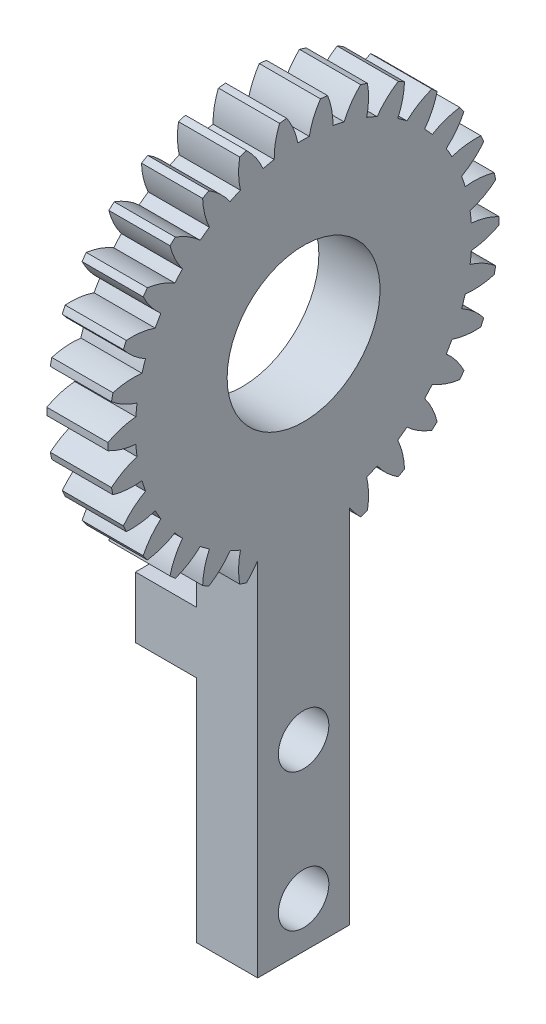
SolidWorks part; units mm, degrees
ref_plane "Plane1" through (0, 0, 0) normal (0, 0, 1) x (1, 0, 0)
ref_plane "Plane2" through (0, 0, 0) normal (0, 1, 0) x (1, 0, 0)
ref_plane "Plane3" through (0, 0, 0) normal (1, 0, 0) x (0, 0, -1)
other "Configuration Table"
sketch "HoldingSke" plane through (0, 0, 0) normal (0, 1, 0) x (1, 0, 0)
  line L0 (0, 0) -> (1.0825, -0.625)
  line L1 (-15, 0) -> (100, 0) construction
  line L2 (0, 0) -> (-2.1039, 2.3779)
  line L3 (0, 0) -> (-11.863, 4.5341)
  line L4 (0, 0) -> (7.479, 4.318)
  line L5 (0, 0) -> (-46.8476, -17.4728)
  line L6 (0, 0) -> (-3.3159, -2.2372)
  line L7 (-2.1039, 2.3779) -> (8.6586, 51.2059)
  line L8 (-76.2, 54.61) -> (-74.4, 54.61)
  line L9 (-71.009, 38.7566) -> (-53.1078, 45.2721)
  line L10 (-76.2, 71.12) -> (104.1128, 71.12)
  line L11 (0, 0) -> (-4, 0)
  line L12 (-76.2, 101.6) -> (-76.17, 101.6)
  line L13 (24.9733, 27.94) -> (52.9518, 28.4284)
  line L14 (24.9733, 27.94) -> (24.9743, 27.94)
  line L15 (24.9733, 27.94) -> (100.4006, 29.5858)
  line L16 (-63.627, -0.8) -> (-12.827, -0.8)
  circle A0 centre (0, 0) radius 5
  circle A1 centre (0, 0) radius 10.999
  circle A2 centre (0, 0) radius 37.5
  circle A3 centre (0, 0) radius 5
  dimension "Num_teeth" = 30
  dimension "Pitch_radius" = 180.3128
  dimension "Width" = 4
  dimension "Thickness" = 4
sketch "BasProSke" plane through (0, 0, 0) normal (0, 1, 0) x (1, 0, 0)
  line L0 (-10, 0) -> (60, 0) construction
  line L1 (0, 0) -> (0, 12.8)
  line L2 (0, 0) -> (4, 0)
  line L3 (4, 0) -> (4, 12.8)
  line L4 (4, 12.8) -> (0, 12.8)
  dimension "Thickness" = 4
  dimension "Diameter" = 25.6
revolve "Base-Revolve" add sketch "BasProSke" angle 360 about L0
sketch "TooCutSke" plane through (0, 0, 0) normal (1, 0, 0) x (0, 0, -1)
  line L1 (0, 0) -> (0, 107) construction
  line L2 (0, 0) -> (-0.6805, 11.9807) construction
  line L3 (0, 0) -> (-2.5058, 23.8411) construction
  line L4 (-0.6805, 11.9807) -> (-1.2529, 11.9205) construction
  arc A0 (0.3724, 10.9927) -> (-0.3724, 10.9927) centre (0, 0) ccw
  arc A1 (1.1205, 12.7764) -> (-1.1205, 12.7764) centre (0, 0) ccw
  circle A2 centre (0, 0) radius 12 construction
  circle A3 centre (0, 0) radius 11.2763 construction
  arc A4 (-0.3724, 10.9927) -> (-1.1205, 12.7764) centre (-5.0822, 10.0661) ccw
  arc A5 (1.1205, 12.7764) -> (0.3724, 10.9927) centre (5.0822, 10.0661) ccw
extrude "ToothCut" cut sketch "TooCutSke" along normal through all
fillet "Breaks" [suppressed] radius 0.016 tangent propagation no
fillet "RootFillets" [suppressed] radius 0.201
pattern_circular "TeethCuts" count 30 every 12 about axis through (-10, 0, 0) along (1, 0, 0) of "ToothCut", "RootFillets", "Breaks"
sketch "HubNeaOneSke" plane through (0, 0, 0) normal (-1, 0, 0) x (0, 0, 1)
  circle A0 centre (0, 0) radius 10.999
  dimension "Diameter" = 21.998
extrude "HubNearOne" [suppressed] add sketch "HubNeaOneSke" along normal blind 46.0001
sketch "HubNeaBotSke" plane through (0, 0, 0) normal (-1, 0, 0) x (0, 0, 1)
  circle A0 centre (0, 0) radius 10.999
  dimension "Diameter" = 21.998
extrude "HubNearBoth" [suppressed] add sketch "HubNeaBotSke" along normal blind 23
ref_plane "FarPln" through (4, 0, 0) normal (1, 0, 0) x (0, 0, -1)
sketch "HubFarSke" plane through (4, 0, 0) normal (1, 0, 0) x (0, 0, -1)
  circle A0 centre (0, 0) radius 10.999
  dimension "Diameter" = 21.998
extrude "HubFar" [suppressed] add sketch "HubFarSke" along normal blind 23
sketch "BorSke" plane through (0, 0, 0) normal (1, 0, 0) x (0, 0, -1)
  circle A0 centre (0, 0) radius 5
  dimension "Diameter" = 10
extrude "Bore" cut sketch "BorSke" along normal mid plane 100.0001
sketch "KeySke" plane through (0, 0, 0) normal (1, 0, 0) x (0, 0, -1)
  line L0 (-2, 0) -> (-2, 6.8)
  line L1 (-2, 6.8) -> (2, 6.8)
  line L2 (2, 6.8) -> (2, 0)
  line L3 (0, 0) -> (0, 34) construction
  line L4 (-2, 0) -> (2, 0)
  dimension "Width" = 4
extrude "Keyway" [suppressed] cut sketch "KeySke" along normal mid plane 100.0001
pattern_circular "Keyway2" [suppressed] count 2 every 90 about axis through (-10, 0, 0) along (1, 0, 0)
sketch "草图1" plane through (4, 0, 0) normal (1, 0, 0) x (0, 0, -1)
  line L0 (0, 1.8258) -> (0, 0) construction
  line L1 (-3, -6.6367) -> (3, -6.6367)
  line L2 (-3, -6.6367) -> (-3, -35)
  line L3 (-3, -35) -> (3, -35)
  line L4 (3, -6.6367) -> (3, -35)
  point P7 (0, -6.6367)
  dimension "D1" = 35
  dimension "D2" = 6
extrude "凸台-拉伸1" add sketch "草图1" against normal blind 4
sketch "草图4" plane through (0, 0, -3) normal (0, 0, -1) x (-1, 0, 0)
  line L1 (0, -35) -> (-2, -35)
  line L2 (0, -35) -> (0, -20)
  line L3 (0, -20) -> (-2, -20)
  line L4 (-2, -35) -> (-2, -20)
  dimension "D1" = 2
  dimension "D2" = 15
extrude "切除-拉伸2" cut sketch "草图4" against normal blind 6
sketch "草图6" plane through (2, 0, 0) normal (-1, 0, 0) x (0, 0, 1)
  line L0 (3, -20) -> (-3, -20) construction
  line L1 (3, -35) -> (-3, -35) construction
  circle A0 centre (0, -23) radius 1.65
  circle A1 centre (0, -32) radius 1.65
  dimension "D1" = 3
  dimension "D3" = 3.3
  dimension "D2" = 3
extrude "切除-拉伸3" cut sketch "草图6" against normal blind 4
sketch "草图7" plane through (4, 0, 0) normal (1, 0, 0) x (0, 0, -1)
  circle A0 centre (0, 0) radius 12
  dimension "D1" = 24
sketch "草图8" plane through (2, 0, 0) normal (-1, 0, 0) x (0, 0, 1)
  line L1 (-3, -20) -> (3, -20)
  line L2 (-3, -20) -> (-3, -35)
  line L3 (-3, -35) -> (3, -35)
  line L4 (3, -20) -> (3, -35)
  circle A0 centre (0, -23) radius 1.65
  circle A1 centre (0, -32) radius 1.65
extrude "凸台-拉伸2" add sketch "草图8" along normal blind 2
sketch "草图9" plane through (0, 0, 3) normal (0, 0, 1) x (1, 0, 0)
  line L0 (0, -11.3438) -> (0, -35) construction
  line L1 (0, -20) -> (-4, -20)
  line L2 (0, -20) -> (0, -16)
  line L3 (0, -16) -> (-4, -16)
  line L4 (-4, -20) -> (-4, -16)
  line L5 (0, -20) -> (-4, -20) construction
  dimension "D1" = 4
extrude "凸台-拉伸3" add sketch "草图9" against normal blind 6
equation "' \"Module@HoldingSke\" = 6.35"
equation "' \"Num_teeth@HoldingSke\" = 12"
equation "' \"Ap@HoldingSke\" =  20"
equation "' \"Ap@HoldingSke\" = 20"
equation "' \"Width@HoldingSke\" = 0.5 * 25.4"
equation "' \"Hub_dia@HoldingSke\"= 1 * 25.4"
equation "' \"Hub_dia@HoldingSke\" = 1 * 25.4"
equation "' \"Overall_len@HoldingSke\" = 1.0 * 25.4"
equation "' \"Bore@HoldingSke\" = 0.75 * 25.4"
equation "' \"T_dim@HoldingSke\" = 0.1 * 25.4"
equation "' \"Width@KeySke\" = 0.25 * 25.4"
equation "' \"Show_teeth@HoldingSke\" = 13"
equation "' \"Backlash@HoldingSke\" = 0.009 * 25.4"
equation "' \"Addendum_fac@HoldingSke\" = 1.0"
equation "' \"Dedendum_fac@HoldingSke\" = 1.25"
equation "' \"Dedendum_add@HoldingSke\" = 0.00005 * 25.4"
equation "' \"Clearance_fac@HoldingSke\" = 0.25"
equation "\"Pitch@HoldingSke\" = 1 / \"Module@HoldingSke\""
equation "\"Overcut_dia@TooCutSke\" = (\"Num_teeth@HoldingSke\" + 2 * \"Addendum_fac@HoldingSke\") / \"Pitch@HoldingSke\" + 0.002 * 25.4"
equation "\"Pitch_dia@TooCutSke\" = \"Num_teeth@HoldingSke\" / \"Pitch@HoldingSke\""
equation "\"Base_dia@TooCutSke\" = \"Num_teeth@HoldingSke\" / \"Pitch@HoldingSke\" * cos((\"Ap@HoldingSke\"  * 3.14159265 / 180))"
equation "\"Root_dia@TooCutSke\" = (\"Num_teeth@HoldingSke\" + 2) / \"Pitch@HoldingSke\" - 2 * (\"Addendum_fac@HoldingSke\" + \"Dedendum_fac@HoldingSke\") / \"Pitch@HoldingSke\" - \"Dedendum_add@HoldingSke\" * 2"
equation "\"Half_ang@TooCutSke\" = 180 / \"Num_teeth@HoldingSke\""
equation "\"Half_CT@TooCutSke\" = \"Num_teeth@HoldingSke\" / \"Pitch@HoldingSke\" * sin((3.14159265 / 2 / \"Num_teeth@HoldingSke\")) / 2 - 7 * \"Backlash@HoldingSke\" / 4"
equation "\"Flank_rad@TooCutSke\" = \"Num_teeth@HoldingSke\" / \"Pitch@HoldingSke\" / 5"
equation "\"Radius@RootFillets\" = \"Clearance_fac@HoldingSke\" / \"Pitch@HoldingSke\" + \"Dedendum_add@HoldingSke\""
equation "\"Break_rad@Breaks\" = 0.02 / \"Pitch@HoldingSke\""
equation "\"Thickness@HoldingSke\" = \"Width@HoldingSke\""
equation "\"OAL@HoldingSke\" = \"Thickness@HoldingSke\""
equation "\"MHD@HoldingSke\" = (\"Num_teeth@HoldingSke\" + 2) / \"Pitch@HoldingSke\" - 2 * (\"Addendum_fac@HoldingSke\" + \"Dedendum_fac@HoldingSke\")  / \"Pitch@HoldingSke\" - \"Dedendum_add@HoldingSke\" * 2"
equation "\"MBD@HoldingSke\" = (\"Num_teeth@HoldingSke\" + 2) / \"Pitch@HoldingSke\" - 2 * (\"Addendum_fac@HoldingSke\" + \"Dedendum_fac@HoldingSke\")  / \"Pitch@HoldingSke\" - \"Dedendum_add@HoldingSke\" * 2 - 0.002 * 25.4"
equation "\"MHD@HoldingSke\" = ((sgn( \"MHD@HoldingSke\" - \"Hub_dia@HoldingSke\" )-1)*( \"MHD@HoldingSke\" - \"Hub_dia@HoldingSke\" ))/-2+ \"Hub_dia@HoldingSke\""
equation "\"MBD@HoldingSke\" = ((sgn( \"MBD@HoldingSke\" - \"Bore@HoldingSke\" )-1)*( \"MBD@HoldingSke\" - \"Bore@HoldingSke\" ))/-2+ \"Bore@HoldingSke\""
equation "\"OAL@HoldingSke\" = ((sgn( \"OAL@HoldingSke\" - \"Overall_len@HoldingSke\" )+1)*( \"OAL@HoldingSke\" - \"Overall_len@HoldingSke\" ))/2 + \"Overall_len@HoldingSke\" + 0.000002 * 25.4"
equation "\"Num_teeth@TeethCuts\" = int( \"Show_teeth@HoldingSke\" ) + 1"
equation "\"Num_teeth@TeethCuts\" = ((sgn( \"Num_teeth@TeethCuts\" - \"Num_teeth@HoldingSke\" )-1)*( \"Num_teeth@TeethCuts\" - \"Num_teeth@HoldingSke\" ))/-2+ \"Num_teeth@HoldingSke\""
equation "\"Num_teeth@TeethCuts\" = ((sgn( \"Num_teeth@TeethCuts\" - 2.0)+1)*( \"Num_teeth@TeethCuts\" - 2.0))/2 +2.0"
equation "\"Angle@TeethCuts\" = 360.0 / \"Num_teeth@HoldingSke\""
equation "\"Diameter@BasProSke\" = (\"Num_teeth@HoldingSke\" + 2 * \"Addendum_fac@HoldingSke\") / \"Pitch@HoldingSke\""
equation "\"Thickness@BasProSke\"  = \"Thickness@HoldingSke\""
equation "' \"Fillet_rad@BasProSke\" =  \"Thickness@HoldingSke\" * 0.05"
equation "' \"Fillet_rad@BasProSke\" = \"Thickness@HoldingSke\" * 0.05"
equation "\"MHD@HoldingSke\" = ((sgn( \"MHD@HoldingSke\" - \"Root_dia@TooCutSke\" )-1)*( \"MHD@HoldingSke\" - \"Root_dia@TooCutSke\" ))/-2+ \"Root_dia@TooCutSke\""
equation "\"Diameter@HubNeaOneSke\" = \"MHD@HoldingSke\""
equation "\"Length@HubNearOne\" = \"OAL@HoldingSke\" - \"Thickness@BasProSke\""
equation "\"Diameter@HubNeaBotSke\" = \"MHD@HoldingSke\""
equation "\"Length@HubNearBoth\" = ( \"OAL@HoldingSke\" - \"Thickness@BasProSke\" ) / 2.0"
equation "\"Thickness@FarPln\" = \"Thickness@BasProSke\""
equation "\"Diameter@HubFarSke\" = \"MHD@HoldingSke\""
equation "\"Length@HubFar\" = ( \"OAL@HoldingSke\" - \"Thickness@BasProSke\" ) / 2.0"
equation "\"Diameter@BorSke\" = \"MBD@HoldingSke\""
equation "\"D1@Bore\" = \"OAL@HoldingSke\" * 2.0"
equation "\"D1@Keyway\" = \"OAL@HoldingSke\" * 2.0"
equation "\"Offset@KeySke\" = \"T_dim@HoldingSke\" + \"MBD@HoldingSke\" / 2.0"
